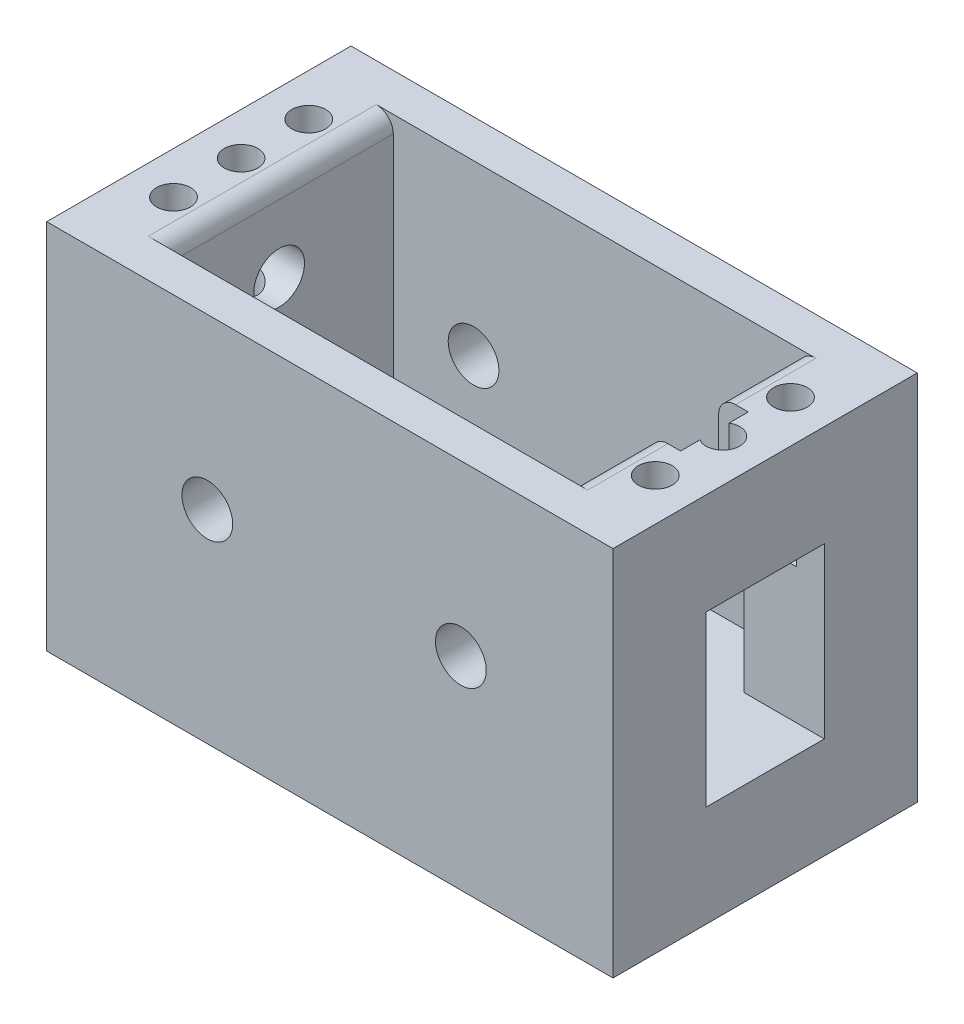
SolidWorks part; units mm, degrees
material "PET"
ref_plane "Alzado" through (0, 0, 0) normal (0, 0, 1) x (1, 0, 0)
ref_plane "Planta" through (0, 0, 0) normal (0, 1, 0) x (1, 0, 0)
ref_plane "Vista lateral" through (0, 0, 0) normal (1, 0, 0) x (0, 0, -1)
sketch "Croquis1" plane through (0, 0, 0) normal (0, 1, 0) x (1, 0, 0)
  line L1 (-16.75, -9) -> (16.75, -9)
  line L2 (-16.75, -9) -> (-16.75, 9)
  line L3 (-16.75, 9) -> (16.75, 9)
  line L4 (16.75, -9) -> (16.75, 9)
  line L5 (-16.75, -9) -> (16.75, 9) construction
  line L6 (-16.75, 9) -> (16.75, -9) construction
  point P0 (0, 0)
  dimension "D1" = 33.5
  dimension "D2" = 18
extrude "Saliente-Extruir1" add sketch "Croquis1" along normal blind 22
sketch "Croquis2" plane through (0, 22, 0) normal (0, 1, 0) x (1, 0, 0)
  line L1 (-11.75, -6.75) -> (11.75, -6.75)
  line L2 (-11.75, -6.75) -> (-11.75, 6.75)
  line L3 (-11.75, 6.75) -> (11.75, 6.75)
  line L4 (11.75, -6.75) -> (11.75, 6.75)
  line L5 (-11.75, -6.75) -> (11.75, 6.75) construction
  line L6 (-11.75, 6.75) -> (11.75, -6.75) construction
  point P0 (0, 0)
  dimension "D1" = 23.5
  dimension "D2" = 13.5
extrude "Cortar-Extruir1" cut sketch "Croquis2" against normal blind 16 contours L2 L1 L4 L3
sketch "Croquis3" plane through (11.75, 0, 0) normal (-1, 0, 0) x (0, 0, 1)
  line L0 (6.75, 6) -> (-6.75, 6) construction
  line L1 (-3.5, 6) -> (3.5, 6)
  line L2 (-3.5, 6) -> (-3.5, 16)
  line L3 (-3.5, 16) -> (3.5, 16)
  line L4 (3.5, 6) -> (3.5, 16)
  point P6 (0, 6)
  point P7 (0, 6)
  dimension "D1" = 10
  dimension "D2" = 7
extrude "Cortar-Extruir2" cut sketch "Croquis3" against normal up to next
sketch "Croquis4" plane through (0, 22, 0) normal (0, 1, 0) x (1, 0, 0)
  line L0 (11.75, 0) -> (16.75, 0) construction
  line L1 (11.75, -6.75) -> (11.75, 6.75) construction
  line L2 (16.75, -9) -> (16.75, 9) construction
  line L3 (-11.55, 0) -> (11.55, 0) construction
  line L4 (0, -9.9) -> (0, 9.9) construction
  circle A0 centre (14.25, 0) radius 1
  circle A1 centre (14.25, 4) radius 1
  circle A2 centre (14.25, -4) radius 1
  circle A3 centre (-14.25, -4) radius 1
  circle A4 centre (-14.25, 0) radius 1
  circle A5 centre (-14.25, 4) radius 1
  dimension "D1" = 2
  dimension "D2" = 4
extrude "Cortar-Extruir3" cut sketch "Croquis4" against normal blind 8
sketch "Croquis5" plane through (0, 22, 0) normal (0, 1, 0) x (1, 0, 0)
  line L0 (11.75, -6.75) -> (11.75, 6.75) construction
  line L1 (11.75, -2) -> (13.75, -2)
  line L2 (11.75, -2) -> (11.75, 2)
  line L3 (11.75, 2) -> (13.75, 2)
  line L4 (13.75, -2) -> (13.75, 2)
  point P6 (11.75, 0)
  point P7 (11.75, 0)
  dimension "D1" = 2
  dimension "D2" = 4
extrude "Cortar-Extruir4" cut sketch "Croquis5" against normal up to next
sketch "Croquis6" plane through (0, 6, 0) normal (0, 1, 0) x (1, 0, 0)
  line L0 (11.75, 2) -> (11.75, 6.75) construction
  circle A0 centre (4.75, 0) radius 1.5
  dimension "D2" = 3
  dimension "D1" = 7
extrude "Cortar-Extruir5" cut sketch "Croquis6" against normal up to next
sketch "Croquis7" plane through (-16.75, 0, 0) normal (-1, 0, 0) x (0, 0, 1)
  line L0 (-9, 22) -> (9, 22) construction
  circle A0 centre (0, 17) radius 1.5
  circle A1 centre (0, 10) radius 1.5
  dimension "D3" = 3
  dimension "D1" = 5
  dimension "D2" = 7
extrude "Cortar-Extruir6" cut sketch "Croquis7" against normal up to next
sketch "Croquis8" plane through (0, 0, -9) normal (0, 0, -1) x (-1, 0, 0)
  line L0 (-16.75, 22) -> (16.75, 22) construction
  line L1 (-16.75, 22) -> (-16.75, 0) construction
  circle A0 centre (-7.75, 12) radius 1.5
  circle A1 centre (7.25, 12) radius 1.5
  dimension "D1" = 3
  dimension "D2" = 10
  dimension "D3" = 9
  dimension "D4" = 15
extrude "Cortar-Extruir7" cut sketch "Croquis8" against normal through all
sketch "Croquis9" plane through (0, 22, 0) normal (0, 1, 0) x (1, 0, 0)
  line L0 (0, -9.9) -> (0, 9.9) construction
  line L1 (-11.75, 6.75) -> (-12, 6.75)
  line L2 (-11.75, 6.75) -> (-11.75, -6.75)
  line L3 (-11.75, -6.75) -> (-12, -6.75)
  line L4 (-12, 6.75) -> (-12, -6.75)
  line L5 (11.75, -6.75) -> (12, -6.75)
  line L6 (12, 6.75) -> (12, -6.75)
  line L7 (11.75, 6.75) -> (12, 6.75)
  line L8 (11.75, 6.75) -> (11.75, -6.75)
  dimension "D1" = 0.25
extrude "Cortar-Extruir8" cut sketch "Croquis9" against normal up to surface (16 mm away) up to face at (4.75, 6, 1.5)
fillet "Redondeo1" radius 1 3 edges at (12, 22, 4.375) (12, 22, -4.375) (-12, 22, 0)
equation "\"A\"= 23.5mm"
equation "\"B\"= 13.5mm"
equation "\"C\"= 16mm"
equation "\"D1@Croquis1\"=\"A\"+10"
equation "\"D2@Croquis1\"=\"B\"+4.50"
